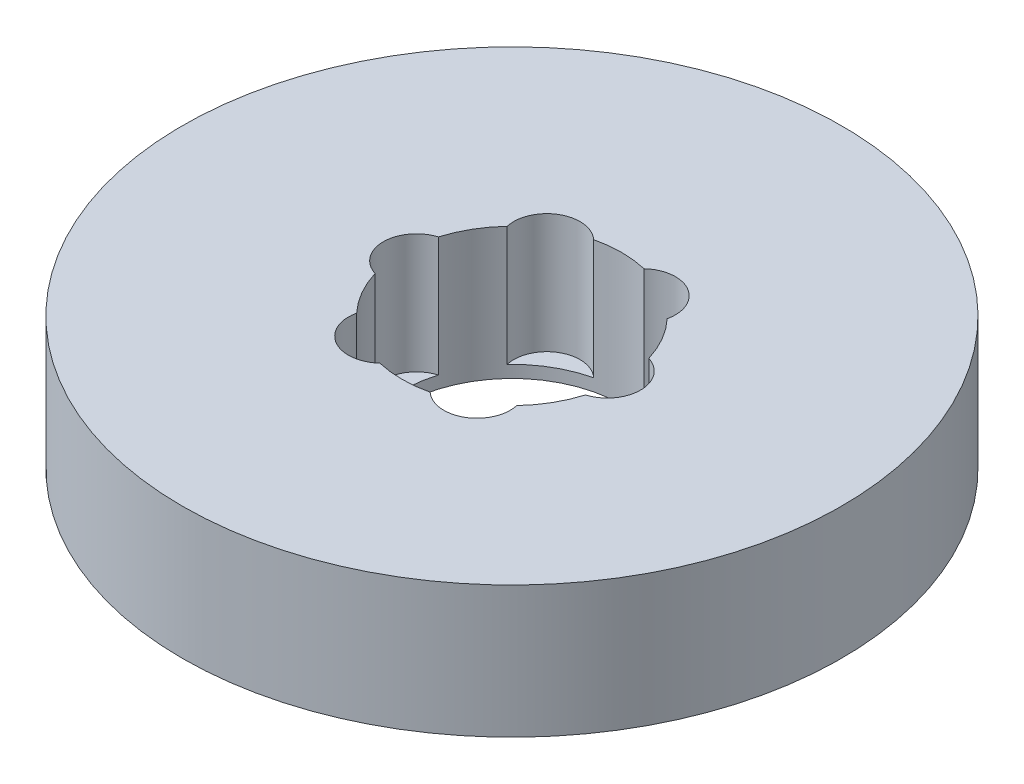
SolidWorks part; units mm, degrees
ref_plane "Front Plane" through (0, 0, 0) normal (0, 0, 1) x (1, 0, 0)
ref_plane "Top Plane" through (0, 0, 0) normal (0, 1, 0) x (1, 0, 0)
ref_plane "Right Plane" through (0, 0, 0) normal (1, 0, 0) x (0, 0, -1)
sketch "Sketch1" plane through (0, 0, 0) normal (0, 1, 0) x (1, 0, 0)
  circle A0 centre (0, 0) radius 45
  dimension "FLANGE_OD" = 90
extrude "Boss-Extrude1" add sketch "Sketch1" along normal blind 18
sketch "Sketch2" plane through (0, 0, 0) normal (0, 1, 0) x (1, 0, 0)
  circle A0 centre (0, 0) radius 15
  dimension "BORE_D" = 30
extrude "Cut-Extrude1" cut sketch "Sketch2" along normal through all
sketch "Sketch3" plane through (0, 18, 0) normal (0, 1, 0) x (1, 0, 0)
  circle A0 centre (0, 0) radius 13.0305 construction
  circle A1 centre (-13.0305, 0) radius 4.5263
  dimension "BOLT_D" = 9.0525
  dimension "BOLT_PCD" = 26.061
extrude "Cut-Extrude2" cut sketch "Sketch3" against normal blind 16.327
pattern_circular "CirPattern1" count 6 over 360 about axis through (0, 0, 0) along (0, 1, 0) of "Cut-Extrude2"
